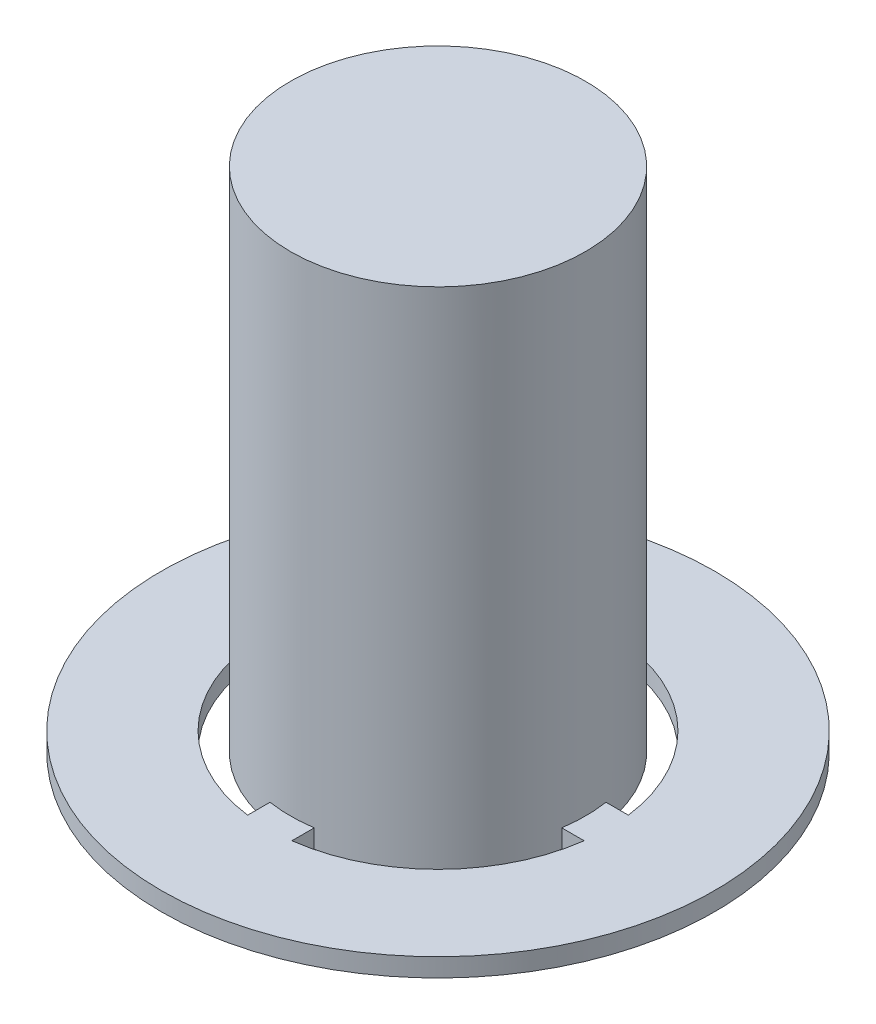
SolidWorks part; units mm, degrees
ref_plane "Front Plane" through (0, 0, 0) normal (0, 0, 1) x (1, 0, 0)
ref_plane "Top Plane" through (0, 0, 0) normal (0, 1, 0) x (1, 0, 0)
ref_plane "Right Plane" through (0, 0, 0) normal (1, 0, 0) x (0, 0, -1)
sketch "Sketch1" plane through (0, 0, 0) normal (0, 1, 0) x (1, 0, 0)
  circle A0 centre (0, 0) radius 4
  dimension "D1" = 8
extrude "Boss-Extrude1" add sketch "Sketch1" along normal blind 13.75
sketch "Sketch2" plane through (0, 0, 0) normal (0, -1, 0) x (-1, 0, 0)
  circle A0 centre (0, 0) radius 7.5
  circle A1 centre (0, 0) radius 4.6
  dimension "D1" = 9.2
  dimension "D2" = 15
extrude "Boss-Extrude2" add sketch "Sketch2" against normal blind 0.5 separate body
sketch "Sketch3" plane through (0, 0, 0) normal (0, -1, 0) x (-1, 0, 0)
  line L1 (6, 0.6) -> (-6, 0.6)
  line L2 (6, 0.6) -> (6, -0.6)
  line L3 (6, -0.6) -> (-6, -0.6)
  line L4 (-6, 0.6) -> (-6, -0.6)
  line L5 (6, 0.6) -> (-6, -0.6) construction
  line L6 (6, -0.6) -> (-6, 0.6) construction
  line L7 (0.6, 6) -> (-0.6, 6)
  line L8 (0.6, 6) -> (0.6, -6)
  line L9 (0.6, -6) -> (-0.6, -6)
  line L10 (-0.6, 6) -> (-0.6, -6)
  line L11 (0.6, 6) -> (-0.6, -6) construction
  line L12 (0.6, -6) -> (-0.6, 6) construction
  point P0 (0, 0)
  point P6 (0, 0)
  circle M1 centre (0, 0) radius 4
  dimension "D1" = 12
  dimension "D2" = 1.2
  dimension "D3" = 12
  dimension "D4" = 1.2
extrude "Boss-Extrude3" add sketch "Sketch3" against normal blind 0.5 contours L7 L10 L8 M1 | L10 L9 L8 M1 | L10 L1 L8 M1 | L3 L10 L8 M1 | L3 L4 L1 L2 region at (0, 0, -2.2925) region at (0, 0, -4.9924) region at (0, 0, 2.2925) region at (0, 0, 4.9924)
